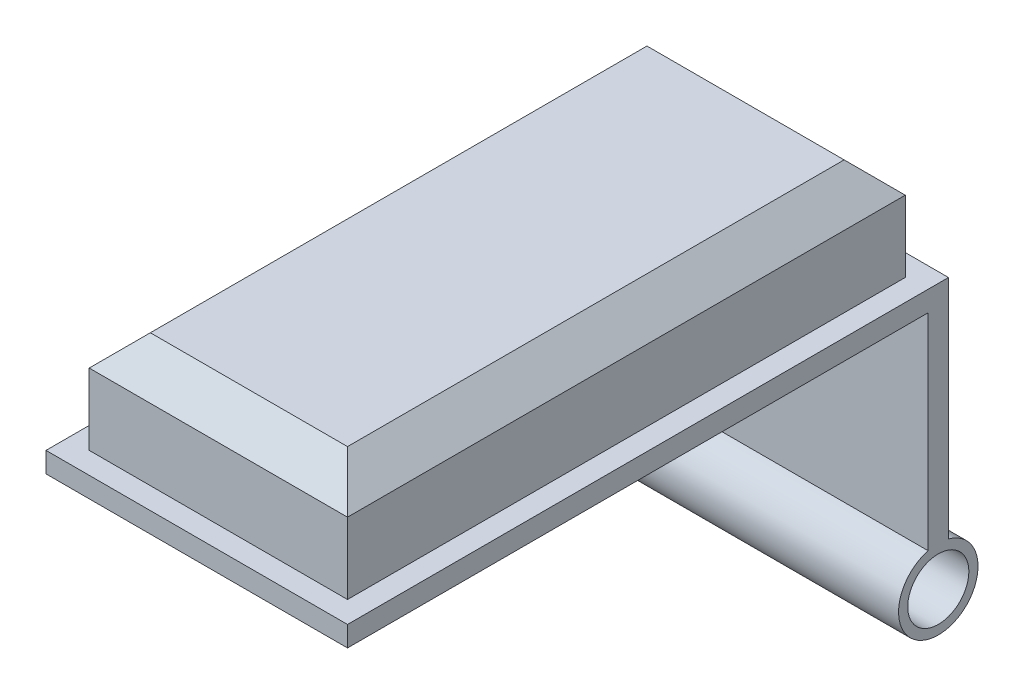
SolidWorks part; units mm, degrees
ref_plane "Front Plane" through (0, 0, 0) normal (0, 0, 1) x (1, 0, 0)
ref_plane "Top Plane" through (0, 0, 0) normal (0, 1, 0) x (1, 0, 0)
ref_plane "Right Plane" through (0, 0, 0) normal (1, 0, 0) x (0, 0, -1)
sketch "Sketch1" plane through (0, 0, 0) normal (1, 0, 0) x (0, 0, -1)
  line L0 (-0.0005, -0.0031) -> (-0.0005, 1.9469)
  line L1 (-0.0005, 12.9969) -> (0.499, 12.9969)
  line L2 (0.499, 12.9969) -> (-0.501, 12.9969)
  line L3 (-0.501, 12.9969) -> (-0.501, 1.8816)
  line L4 (0.499, 12.9969) -> (0.499, 1.8819)
  arc A0 (-0.501, 1.8816) -> (0.499, 1.8819) centre (-0.0005, -0.0031) ccw
  circle A1 centre (-0.0005, -0.0031) radius 1.5
extrude "Boss-Extrude1" add sketch "Sketch1" along normal blind 14.8 contours L3 A0 L4 L1 L2 A1 region at (0, 5.1785, 0.0008)
ref_plane "Plane1" through (14.8, 12.9969, -0.499) normal (-1, 0, 0) x (0, 0, 1)
sketch "Sketch4" plane through (0, 12.9969, 0) normal (0, 1, 0) x (1, 0, 0)
  line L0 (0, 0) -> (0, -29)
  line L1 (14.8, 4.569) -> (14.8, -3.571) construction
  line L2 (0, -29) -> (14.8, -29)
  line L3 (0, -29) -> (0, 0)
  line L4 (0, 0) -> (14.8, 0)
  line L5 (14.8, -29) -> (14.8, 0)
  line M7 (0, -0.501) -> (14.8, -0.501)
extrude "Boss-Extrude2" add sketch "Sketch4" against normal blind 1 contours L2 L5 L0 M7 region at (7.4, 12.9969, 14.7505)
sketch "Sketch5" plane through (0, 12.9969, 0) normal (0, 1, 0) x (1, 0, 0)
  line L0 (0, 0.499) -> (1.0607, -0.5617)
  line L1 (14.8, -29) -> (13.7393, -27.9393)
  line L3 (1.0607, -0.5617) -> (13.7393, -0.5617)
  line L4 (1.0607, -0.5617) -> (1.0607, -27.9393)
  line L5 (1.0607, -27.9393) -> (13.7393, -27.9393)
  line L6 (13.7393, -0.5617) -> (13.7393, -27.9393)
extrude "Boss-Extrude3" add sketch "Sketch5" along normal blind 5 contours L6 L3 L4 L5 region at (7.4, 12.9969, 14.2505)
chamfer "Chamfer1" distance 1.5 angle 45 4 edges at (7.4, 17.9969, 27.9393) (1.0607, 17.9969, 14.2505) (7.4, 17.9969, 0.5617) (13.7393, 17.9969, 14.2505)
split "Split1" bodies to split 103 resulting bodies 104 105 split by face at (7.4, 12.9969, 14.2505)
